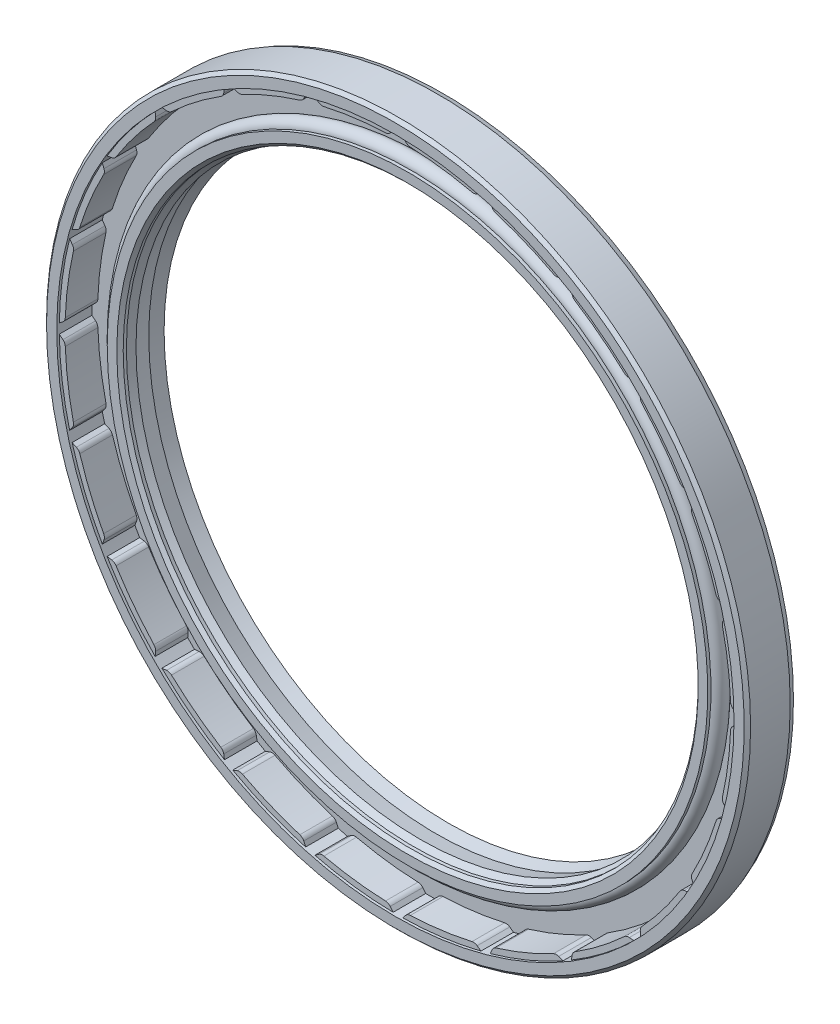
SolidWorks part; units mm, degrees
material "Polyseal Lubrithane"
ref_plane "Front Plane" through (0, 0, 0) normal (0, 0, 1) x (1, 0, 0)
ref_plane "Top Plane" through (0, 0, 0) normal (0, 1, 0) x (1, 0, 0)
ref_plane "Right Plane" through (0, 0, 0) normal (1, 0, 0) x (0, 0, -1)
sketch "Sketch1" plane through (0, 0, 0) normal (1, 0, 0) x (0, 0, -1)
  line L0 (0, 0) -> (-8.7293, 0) construction
  line L1 (0, 45.75) -> (0, 48)
  line L2 (-4.6, 45) -> (-5.1, 45)
  line L3 (-0.8, 55.1) -> (-7, 55.1)
  line L4 (-7.5, 54.6) -> (-7.5, 53)
  line L5 (-7.1, 52.1) -> (-2, 52.1)
  line L6 (-2, 52.1) -> (-2, 47)
  line L7 (-2, 47) -> (-2.6, 47)
  line L8 (-5.6, 45.5) -> (-5.6, 47)
  line L9 (0, 52.5) -> (-0.2, 52.5)
  line L10 (-0.2, 52.5) -> (-0.2, 48)
  line L11 (-0.2, 48) -> (0, 48)
  line L12 (0, 45.75) -> (0.8, 44.5)
  line L13 (-1.1, 45) -> (0.8, 44.5)
  line L14 (0, 52.5) -> (0, 54.8088)
  line L15 (-1.1, 45) -> (-3.6, 44.5)
  line L16 (-3.6, 44.5) -> (-4.6, 45)
  line L17 (0, 54.8088) -> (-0.8, 55.1)
  line L18 (-7, 55.1) -> (-7.5, 54.6)
  line L19 (-7.5, 53) -> (-7.1, 53)
  line L20 (-7.1, 53) -> (-7.1, 52.1)
  line L21 (-5.6, 47) -> (-5.1, 47)
  line L23 (-5.6, 45.5) -> (-5.1, 45)
  arc A0 (-5.1, 47) -> (-2.6, 47) centre (-3.85, 47) cw
  point P21 (-7.5, 55.1)
  dimension "D8" = 1.9
  dimension "D9" = 4.5
  dimension "D10" = 91.5
  dimension "D4" = 1.25
  dimension "D1" = 7.5
  dimension "D3" = 2
  dimension "D5" = 3
  dimension "D6" = 110.2
  dimension "D7" = 90
  dimension "D11" = 105
  dimension "D12" = 96
  dimension "D13" = 0.2
  dimension "D14" = 0.8
  dimension "D15" = 45
  dimension "D16" = 20
  dimension "D17" = 0.8
  dimension "D18" = 106
  dimension "D19" = 0.4
  dimension "D21" = 0.5
  dimension "D22" = 1
  dimension "D23" = 2
  dimension "D24" = 10.6
  dimension "D25" = 94
  dimension "D26" = 0.5
revolve "Revolve1" add sketch "Sketch1" angle 360 about L0
ref_axis "Axis1" through (0, 0, 7) along (0, 0, -1)
sketch "Sketch2" plane through (0, 0, 7.5) normal (0, 0, 1) x (1, 0, 0)
  line L0 (0, 0) -> (0, 81.6309) construction
  line L1 (-0.75, 52.9947) -> (-1.5, 52.0784)
  line L2 (0.75, 52.9947) -> (1.5, 52.0784)
  circle A0 centre (0, 0) radius 53 construction
  arc A2 (0.75, 52.9947) -> (-0.75, 52.9947) centre (0, 0) ccw
  arc A3 (1.5, 52.0784) -> (-1.5, 52.0784) centre (0, 0) ccw
  circle A4 centre (0, 0) radius 52.1 construction
  dimension "D1" = 1.5
  dimension "D2" = 3
extrude "Cut-Extrude1" cut sketch "Sketch2" against normal up to surface (5.5 mm away) up to face at (-47, 0, 2)
fillet "Fillet3" radius 1 2 edges at (1.5, 52.0784, 4.55) (-1.5, 52.0784, 4.55)
pattern_circular "CirPattern1" count 24 over 360 about axis through (0, 0, 0) along (0, 0, -1) of "Cut-Extrude1", "Fillet3"
sketch "Sketch3" plane through (0, 0, 0.2) normal (0, 0, -1) x (-1, 0, 0)
  arc A0 (-51, 0) -> (26.1878, 43.763) centre (0, 0) ccw construction
  text T0 "90-110-7.5/8.5     CORTECO     CFW    BAB4SL"
  dimension "D1" = 51
extrude "Boss-Extrude1" add sketch "Sketch3" along normal blind 0.1
